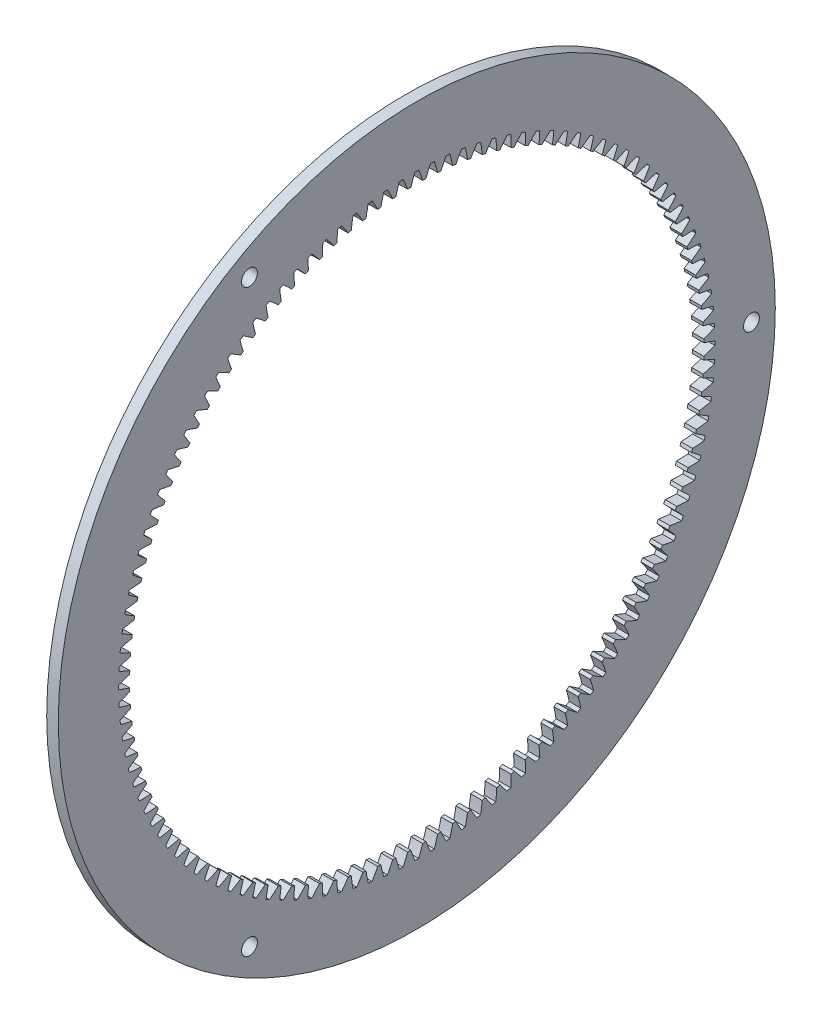
SolidWorks part; units mm, degrees
ref_plane "Plane1" through (0, 0, 0) normal (0, 0, 1) x (1, 0, 0)
ref_plane "Plane2" through (0, 0, 0) normal (0, 1, 0) x (1, 0, 0)
ref_plane "Plane3" through (0, 0, 0) normal (1, 0, 0) x (0, 0, -1)
sketch "HoldingSke" plane through (0, 0, 0) normal (0, 1, 0) x (1, 0, 0)
  line L0 (0, 0) -> (-0.25, -0.433)
  line L1 (-15, 0) -> (100, 0) construction
  line L2 (0, 0) -> (-2.1039, 2.3779)
  line L3 (0, 0) -> (-11.863, 4.5341)
  line L4 (0, 0) -> (-4.318, 7.479)
  line L5 (0, 0) -> (-23.7986, -8.8762)
  line L6 (0, 0) -> (-10.5278, -7.1032)
  line L7 (-2.1039, 2.3779) -> (3.3635, 27.1825)
  line L8 (-76.2, 4.3779) -> (-54.61, 4.3779)
  line L9 (-71.009, 38.7566) -> (-53.1078, 45.2721)
  line L10 (-76.2, 71.12) -> (104.1128, 71.12)
  line L11 (0, 0) -> (-4.7625, 0)
  line L12 (-76.2, 101.6) -> (-76.133, 101.6)
  line L13 (24.9733, 27.94) -> (52.9518, 28.4284)
  line L14 (24.9733, 27.94) -> (24.9743, 27.94)
  line L15 (24.9733, 27.94) -> (100.4006, 29.5858)
  circle A0 centre (0, 0) radius 147.32
  circle A1 centre (0, 0) radius 12.7
  circle A2 centre (0, 0) radius 12.7
  dimension "Num_teeth" = 120
  dimension "Pitch_radius" = 180.3128
  dimension "Width" = 4.7625
  dimension "Diameter" = 294.64
sketch "BasProSke" plane through (0, 0, 0) normal (0, 1, 0) x (1, 0, 0)
  line L0 (-10, 0) -> (60, 0) construction
  line L1 (0, 118) -> (0, 147.32)
  line L2 (0, 118) -> (4.7625, 118)
  line L3 (4.7625, 118) -> (4.7625, 147.32)
  line L4 (4.7625, 147.32) -> (0, 147.32)
  dimension "Thickness" = 4.7625
  dimension "Diameter" = 294.64
revolve "Base-Revolve" add sketch "BasProSke" angle 360 about L0
sketch "TooCutSke" plane through (0, 0, 0) normal (1, 0, 0) x (0, 0, -1)
  line L3 (1.7383, 119.9874) -> (1.7383, 53.6633) construction
  line L4 (0, 0) -> (0, 59.563) construction
  line L5 (0, 0) -> (-1.7886, 68.3041) construction
  line L6 (-54.8647, 100.0849) -> (35.1732, 102.4426) construction
  circle A0 centre (0, 0) radius 120 construction
  circle A1 centre (0, 0) radius 122.501 construction
  circle A2 centre (0, 0) radius 101.4868 construction
  circle A3 centre (0, 0) radius 117.9746 construction
  arc A4 (2.414, 117.9499) -> (0.7917, 122.4984) centre (-54.8647, 100.0849) ccw
  arc A5 (2.414, 117.9499) -> (-2.414, 117.9499) centre (0, 0) ccw
  arc A6 (0.7917, 122.4984) -> (-0.7917, 122.4984) centre (0, 0) ccw
  arc A7 (-0.7917, 122.4984) -> (-2.414, 117.9499) centre (54.8647, 100.0849) ccw
extrude "ToothCut" cut sketch "TooCutSke" along normal through all
fillet "Breaks" [suppressed] radius 0.2
fillet "RootFillets" [suppressed] radius 0.501
pattern_circular "TeethCuts" count 120 every 3 about axis through (-10, 0, 0) along (1, 0, 0) of "RootFillets", "Breaks", "ToothCut"
sketch "Sketch1" plane through (4.7625, 0, 0) normal (1, 0, 0) x (0, 0, -1)
  line L1 (0, 158.7713) -> (-137.5, 79.3857) construction
  line L2 (-137.5, 79.3857) -> (-137.5, -79.3857) construction
  line L3 (-137.5, -79.3857) -> (0, -158.7713) construction
  line L4 (0, -158.7713) -> (137.5, -79.3857) construction
  line L5 (137.5, -79.3857) -> (137.5, 79.3857) construction
  line L6 (137.5, 79.3857) -> (0, 158.7713) construction
  circle A0 centre (0, 0) radius 137.5 construction
  circle A1 centre (-68.75, 119.0785) radius 3.2639
  circle A2 centre (137.5, 0) radius 3.2639
  circle A3 centre (-68.75, -119.0785) radius 3.2639
  point P23 (0, 0)
  dimension "D2" = 6.5278
  dimension "D1" = 158.7713
  dimension "D4" = 137.5
  dimension "D3" = 3
extrude "Cut-Extrude1" cut sketch "Sketch1" against normal through all
equation "' \"Module@HoldingSke\" = 6.35"
equation "' \"Num_teeth@HoldingSke\" = 24"
equation "' \"Ap@HoldingSke\" =  14.5"
equation "' \"Ap@HoldingSke\" = 14.5"
equation "' \"Width@HoldingSke\" = 12"
equation "' \"Diameter@HoldingSke\" = 8 * 25.4"
equation "' \"Show_teeth@HoldingSke\" = 100"
equation "' \"Backlash@HoldingSke\" = 0.009 * 25.4"
equation "' \"Addendum_fac@HoldingSke\" = 1.0"
equation "' \"Dedendum_fac@HoldingSke\" = 1.25"
equation "' \"Dedendum_add@HoldingSke\" = 0.00005 * 25.4"
equation "' \"Clearance_fac@HoldingSke\" = 0.25"
equation "\"Pitch@HoldingSke\" = 1 / \"Module@HoldingSke\" "
equation "\"Overcut_dia@TooCutSke\" = (\"Num_teeth@HoldingSke\" - 2 * \"Addendum_fac@HoldingSke\") / \"Pitch@HoldingSke\" - 0.002 * 25.4"
equation "\"Pitch_dia@TooCutSke\" = \"Num_teeth@HoldingSke\" / \"Pitch@HoldingSke\""
equation "\"Base_dia@TooCutSke\" = \"Num_teeth@HoldingSke\" / \"Pitch@HoldingSke\" * cos((\"Ap@HoldingSke\"  * 3.14159265 / 180)) * 0.90"
equation "\"Root_dia@TooCutSke\" = \"Num_teeth@HoldingSke\"  / \"Pitch@HoldingSke\" + 2 *  \"Dedendum_fac@HoldingSke\"/ \"Pitch@HoldingSke\" + \"Dedendum_add@HoldingSke\" * 2"
equation "\"Half_ang@TooCutSke\" = 180 / \"Num_teeth@HoldingSke\""
equation "\"Half_CT@TooCutSke\" = \"Num_teeth@HoldingSke\" / \"Pitch@HoldingSke\" * sin((3.14159265 / 2 / \"Num_teeth@HoldingSke\")) / 2 + 10 * \"Backlash@HoldingSke\" / 4"
equation "\"Flank_rad@TooCutSke\" = \"Num_teeth@HoldingSke\" / \"Pitch@HoldingSke\" / 4"
equation "\"Radius@RootFillets\"= \"Clearance_fac@HoldingSke\" / \"Pitch@HoldingSke\" + \"Dedendum_add@HoldingSke\""
equation "\"Break_rad@Breaks\" = 0.02 / \"Pitch@HoldingSke\" * 5"
equation "\"Num_teeth@TeethCuts\" = int( \"Show_teeth@HoldingSke\" ) + 1"
equation "\"Num_teeth@TeethCuts\" = ((sgn( \"Num_teeth@TeethCuts\" - \"Num_teeth@HoldingSke\" )-1)*( \"Num_teeth@TeethCuts\" - \"Num_teeth@HoldingSke\" ))/-2+ \"Num_teeth@HoldingSke\""
equation "\"Num_teeth@TeethCuts\" = ((sgn( \"Num_teeth@TeethCuts\" - 2.0)+1)*( \"Num_teeth@TeethCuts\" - 2.0))/2 +2.0"
equation "\"Angle@TeethCuts\" = 360.0 / \"Num_teeth@HoldingSke\""
equation "\"Diameter@BasProSke\" = \"Num_teeth@HoldingSke\"  / \"Pitch@HoldingSke\" + 2 *  \"Dedendum_fac@HoldingSke\"/ \"Pitch@HoldingSke\" + \"Dedendum_add@HoldingSke\" * 2 + 0.002 * 25.4"
equation "\"Diameter@BasProSke\" = ((sgn( \"Diameter@BasProSke\"  - \"Diameter@HoldingSke\" )+1)*( \"Diameter@BasProSke\"  - \"Diameter@HoldingSke\" ))/2 + \"Diameter@HoldingSke\""
equation "\"Inside_diameter@BasProSke\" =  (\"Num_teeth@HoldingSke\" - 2 * \"Addendum_fac@HoldingSke\") / \"Pitch@HoldingSke\" "
equation "\"Thickness@BasProSke\"  = \"Width@HoldingSke\""
equation "\"D1@Sketch1\"=6.25083953in"
